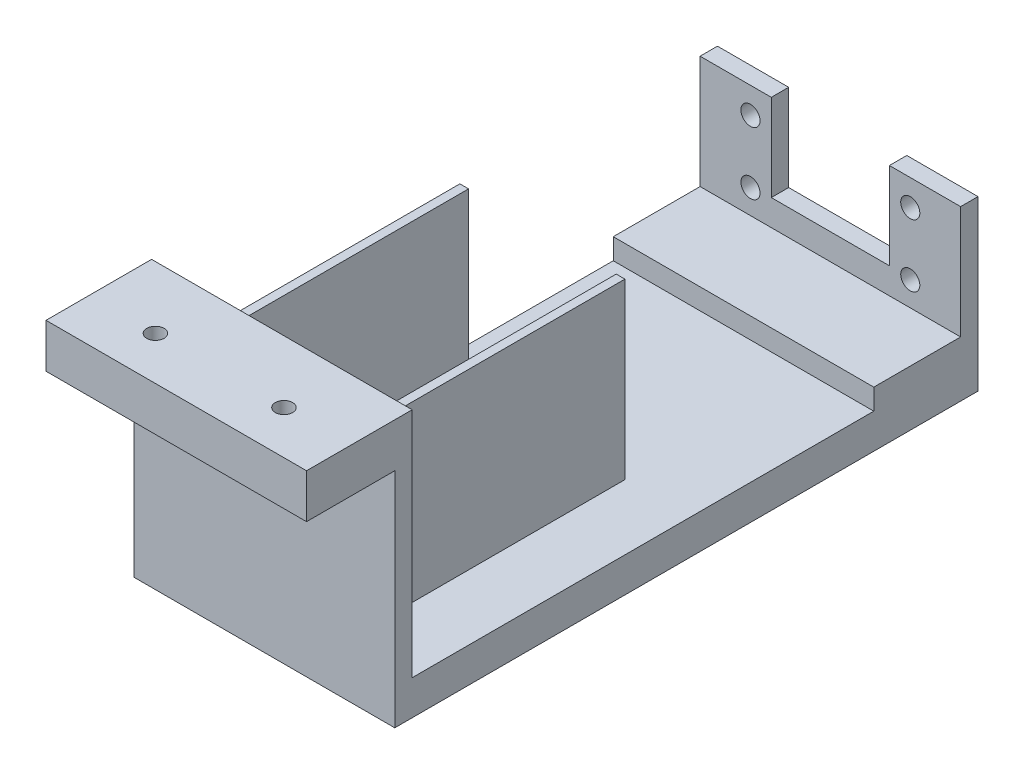
SolidWorks part; units mm, degrees
material "ABS"
ref_plane "Front Plane" through (0, 0, 0) normal (0, 0, 1) x (1, 0, 0)
ref_plane "Top Plane" through (0, 0, 0) normal (0, 1, 0) x (1, 0, 0)
ref_plane "Right Plane" through (0, 0, 0) normal (1, 0, 0) x (0, 0, -1)
sketch "Sketch1" plane through (0, 0, 0) normal (0, 0, 1) x (1, 0, 0)
  line L0 (20.5, 32.5) -> (20.5, 7.5)
  line L1 (0, 0) -> (75, 0)
  line L2 (0, 0) -> (0, 32.5)
  line L3 (0, 32.5) -> (75, 32.5)
  line L4 (75, 0) -> (75, 32.5)
  line L5 (20.5, 7.5) -> (54.5, 7.5)
  line L6 (54.5, 7.5) -> (54.5, 32.5)
  line L7 (37.5, 32.5) -> (37.5, 0) construction
  circle A0 centre (14.5, 25) radius 2.75
  circle A1 centre (14.5, 7) radius 2.75
  circle A2 centre (60.5, 7) radius 2.75
  circle A3 centre (60.5, 25) radius 2.75
  dimension "D6" = 5.5
  dimension "D7" = 46
  dimension "D8" = 34
  dimension "D1" = 32.5
  dimension "D2" = 75
  dimension "D3" = 17
  dimension "D4" = 18
  dimension "D5" = 25
  dimension "D9" = 25
  dimension "D10" = 14.5
  dimension "D11" = 6
extrude "Boss-Extrude1" add sketch "Sketch1" along normal blind 5 contours L7 L5 L0 L3 L2 L1 A1 A0 | L5 L7 L1 L4 L3 L6 A3 A2 region at (13.183, 14.1302, 0) region at (61.817, 14.1302, 0)
sketch "Sketch2" plane through (0, 0, 5) normal (0, 0, 1) x (1, 0, 0)
  line L0 (75, 0) -> (75, 32.5) construction
  line L1 (0, 0) -> (75, 0)
  line L2 (0, 0) -> (0, -6)
  line L3 (0, -6) -> (75, -6)
  line L4 (75, 0) -> (75, -6)
  dimension "D1" = 6
extrude "Boss-Extrude2" add sketch "Sketch2" along normal blind 25 and the other way blind 5
sketch "Sketch3" plane through (0, 0, 0) normal (0, 0, -1) x (-1, 0, 0)
  line L0 (0, -6) -> (0, 32.5) construction
  line L1 (-75, -6) -> (0, -6)
  line L2 (-75, -6) -> (-75, -16)
  line L3 (-75, -16) -> (0, -16)
  line L4 (0, -6) -> (0, -16)
  dimension "D1" = 10
extrude "Boss-Extrude3" add sketch "Sketch3" against normal blind 167.8942
sketch "Sketch4" plane through (0, -6, 0) normal (0, 1, 0) x (1, 0, 0)
  line L0 (75, -167.8942) -> (75, -30) construction
  line L1 (0, -167.8942) -> (75, -167.8942)
  line L2 (0, -167.8942) -> (0, -162.8942)
  line L3 (0, -162.8942) -> (75, -162.8942)
  line L4 (75, -167.8942) -> (75, -162.8942)
  dimension "D1" = 5
extrude "Boss-Extrude4" add sketch "Sketch4" along normal blind 66.8
sketch "Sketch5" plane through (0, 0, 167.8942) normal (0, 0, 1) x (1, 0, 0)
  line L0 (0, -16) -> (0, 60.8) construction
  line L1 (0, 48.1) -> (75, 48.1)
  line L2 (0, 48.1) -> (0, 60.8)
  line L3 (0, 60.8) -> (75, 60.8)
  line L4 (75, 48.1) -> (75, 60.8)
  line L5 (75, 60.8) -> (75, -16) construction
  line L6 (0, 60.8) -> (75, 60.8) construction
  dimension "D2" = 12.7
extrude "Boss-Extrude5" add sketch "Sketch5" along normal blind 25.4
sketch "Sketch8" plane through (0, 0, 162.8942) normal (0, 0, -1) x (-1, 0, 0)
  line L0 (-75, 27.4) -> (0, 27.4) construction
  line L1 (-75, 60.8) -> (-75, -6) construction
  line L2 (0, 60.8) -> (0, -6) construction
  line L3 (-58.75, 49) -> (-58.75, -1)
  line L4 (-58.75, 49) -> (-61.25, 49)
  line L5 (-37.5, 60.8) -> (-37.5, -6) construction
  line L6 (-75, 60.8) -> (0, 60.8) construction
  line L7 (-75, -6) -> (0, -6) construction
  line L8 (-61.25, 49) -> (-61.25, -1)
  line L9 (-61.25, -1) -> (-58.75, -1)
  line L10 (-13.75, -1) -> (-16.25, -1)
  line L11 (-16.25, 49) -> (-16.25, -1)
  line L12 (-16.25, 49) -> (-13.75, 49)
  line L13 (-13.75, 49) -> (-13.75, -1)
  dimension "D1" = 42.5
  dimension "D2" = 2.5
  dimension "D3" = 50
  dimension "D4" = 5
extrude "Boss-Extrude6" add sketch "Sketch8" along normal blind 75
sketch "Sketch9" plane through (0, 60.8, 0) normal (0, 1, 0) x (1, 0, 0)
  line L0 (75, -193.2942) -> (0, -193.2942) construction
  line L1 (0, -162.8942) -> (0, -193.2942) construction
  circle A0 centre (56, -180.7942) radius 2.5
  circle A1 centre (19, -180.7942) radius 2.5
  dimension "D2" = 5
  dimension "D3" = 5
  dimension "D1" = 12.5
  dimension "D4" = 19
extrude "Cut-Extrude1" cut sketch "Sketch9" against normal through all
